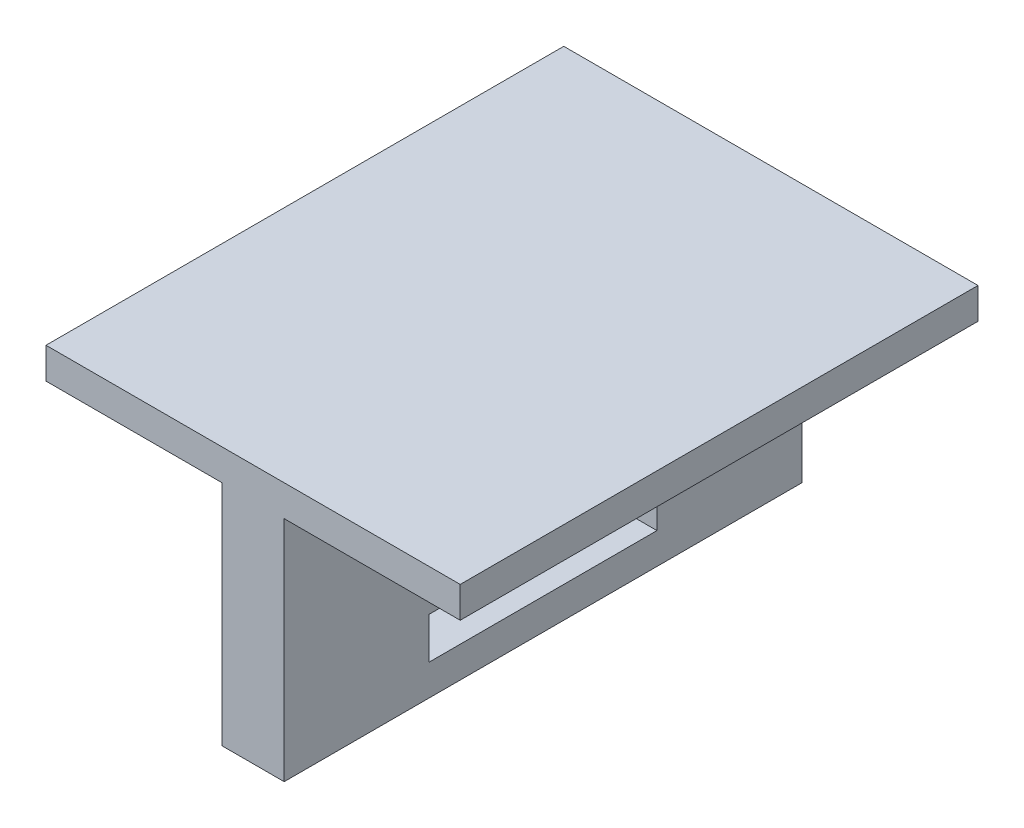
SolidWorks part; units mm, degrees
ref_plane "Front Plane" through (0, 0, 0) normal (0, 0, 1) x (1, 0, 0)
ref_plane "Top Plane" through (0, 0, 0) normal (0, 1, 0) x (1, 0, 0)
ref_plane "Right Plane" through (0, 0, 0) normal (1, 0, 0) x (0, 0, -1)
sketch "Sketch2" plane through (0, 0, 0) normal (1, 0, 0) x (0, 0, -1)
  line L0 (-25, 9.5) -> (25, 9.5)
  line L1 (-25, -12.5) -> (25, -12.5)
  line L2 (-25, -12.5) -> (-25, 12.5)
  line L3 (-25, 12.5) -> (25, 12.5)
  line L4 (25, -12.5) -> (25, 12.5)
  line L5 (-25, -12.5) -> (25, 12.5) construction
  line L6 (-25, 12.5) -> (25, -12.5) construction
  line L7 (-11, -9.5) -> (11, -9.5)
  line L8 (-11, -9.5) -> (-11, -5.5)
  line L9 (-11, -5.5) -> (11, -5.5)
  line L10 (11, -9.5) -> (11, -5.5)
  line L11 (-11, -9.5) -> (11, -5.5) construction
  line L12 (-11, -5.5) -> (11, -9.5) construction
  line L13 (0, -7.5) -> (0, 12.5) construction
  point P0 (0, 0)
  point P6 (0, -7.5)
  dimension "D1" = 20
  dimension "D2" = 4
  dimension "D3" = 22
  dimension "D4" = 3
  dimension "D5" = 50
  dimension "D6" = 25
extrude "Boss-Extrude2" add sketch "Sketch2" along normal blind 3 and the other way blind 3 contours L1 L4 L0 L2 L10 L7 L8 L9 region at (0, -0.9783, 0)
extrude "Boss-Extrude3" add sketch "Sketch2<3>" along normal blind 20 and the other way blind 20 contours L0 L4 L3 L2 region at (0, 11, 0)
sketch "Sketch2<3>" plane through (0, 0, 0) normal (1, 0, 0) x (0, 0, -1) same geometry as "Sketch2"
equation "\"CableDiameter\"=2"
equation "\"D2@Sketch2\"= 2 + \"CableDiameter\""
